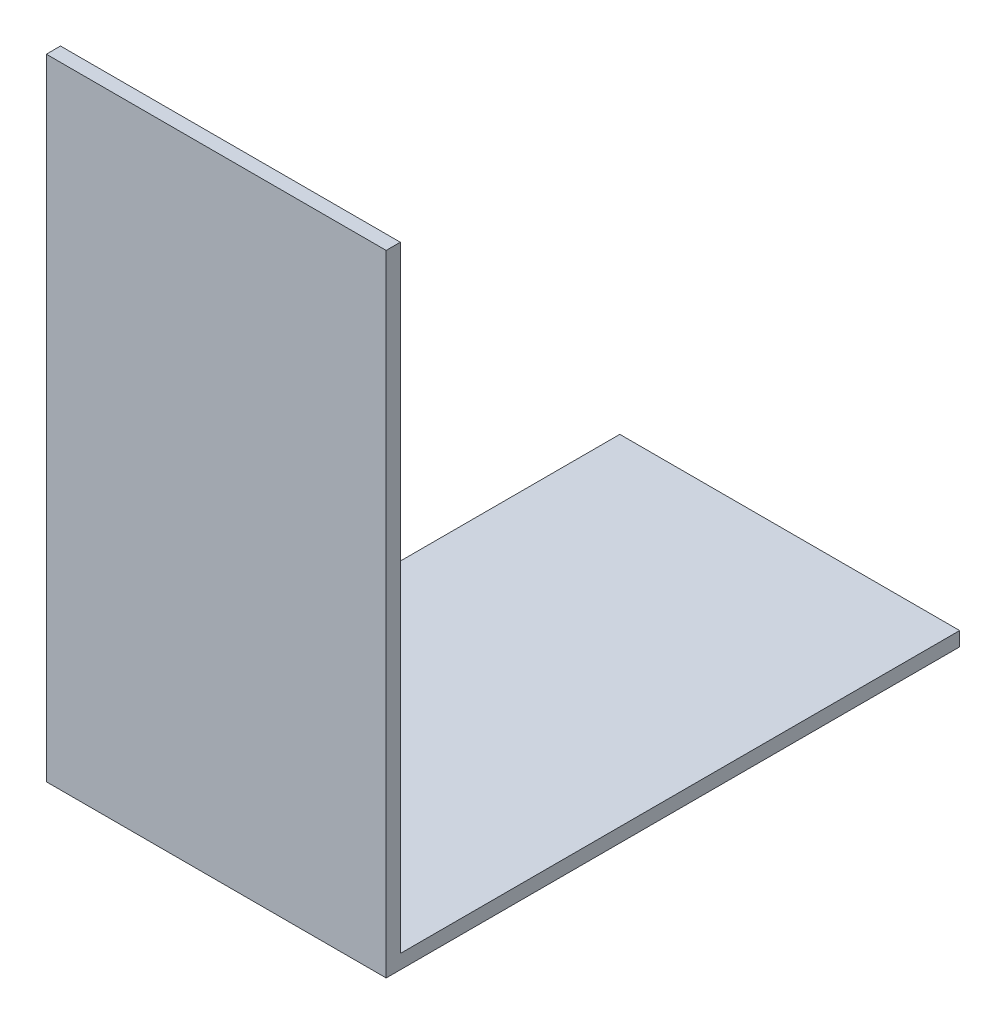
SolidWorks part; units mm, degrees
ref_plane "Front Plane" through (0, 0, 0) normal (0, 0, 1) x (1, 0, 0)
ref_plane "Top Plane" through (0, 0, 0) normal (0, 1, 0) x (1, 0, 0)
ref_plane "Right Plane" through (0, 0, 0) normal (1, 0, 0) x (0, 0, -1)
sketch "Sketch1" plane through (0, 0, 0) normal (1, 0, 0) x (0, 0, -1)
  line L0 (0, 279.4) -> (0, 0) construction
  line L1 (0, 0) -> (254, 0) construction
  line L2 (-3.175, 279.4) -> (-3.175, -3.175)
  line L3 (-3.175, -3.175) -> (254, -3.175)
  line L4 (3.175, 279.4) -> (3.175, 3.175)
  line L5 (3.175, 3.175) -> (254, 3.175)
  line L6 (-3.175, 279.4) -> (3.175, 279.4)
  line L7 (254, -3.175) -> (254, 3.175)
  point P2 (2.7709, 0)
  point P4 (0, 0)
  dimension "D1" = 254
  dimension "D2" = 279.4
  dimension "D3" = 3.175
  dimension "D4" = 3.175
extrude "Boss-Extrude1" add sketch "Sketch1" along normal mid plane 152.4
